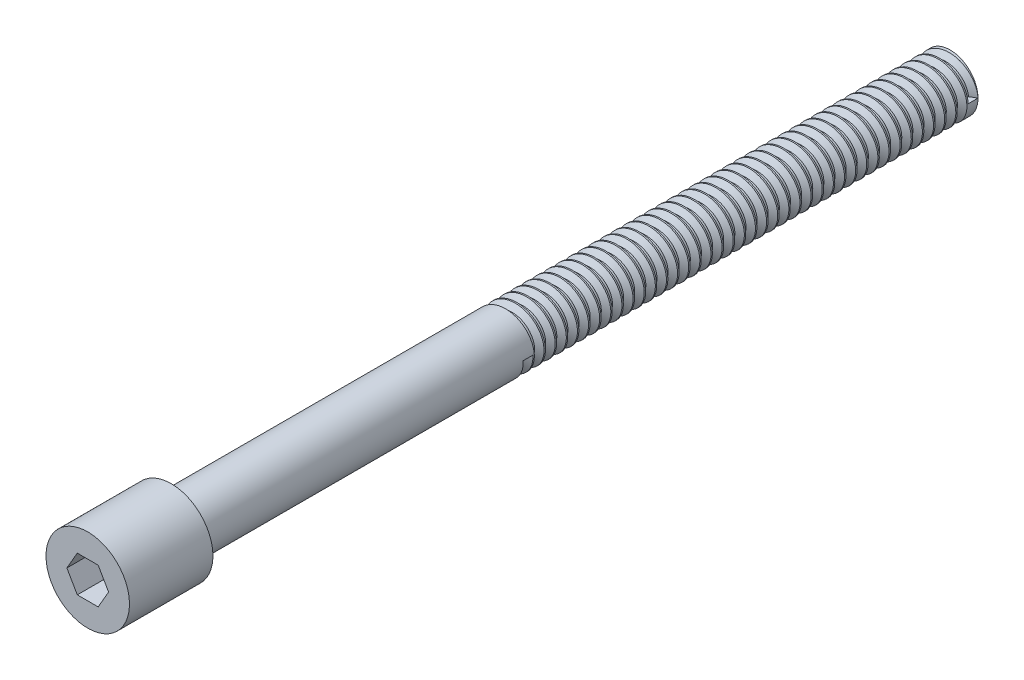
SolidWorks part; units mm, degrees
ref_plane "Front Plane" through (0, 0, 0) normal (0, 0, 1) x (1, 0, 0)
ref_plane "Top Plane" through (0, 0, 0) normal (0, 1, 0) x (1, 0, 0)
ref_plane "Right Plane" through (0, 0, 0) normal (1, 0, 0) x (0, 0, -1)
sketch "Sketch1" plane through (0, 0, 0) normal (0, 0, 1) x (1, 0, 0)
  circle A0 centre (0, 0) radius 3.175
  dimension "D1" = 6.35
extrude "Boss-Extrude1" add sketch "Sketch1" along normal blind 88.9
sketch "Sketch2" plane through (0, 0, 88.9) normal (0, 0, 1) x (1, 0, 0)
  circle A0 centre (0, 0) radius 4.7625
  dimension "D1" = 9.525
extrude "Boss-Extrude2" add sketch "Sketch2" along normal blind 9.525
thread "Thread1" pitch 1.27 method cut profile "Thread Profile1" start angle 0, offset 0, length 50.8, pitch 1.27, diameter 6.35
ref_plane "Plane1" through (3.175, 0, 0) normal (0, -1, 0) x (1, 0, 0)
sketch "Thread Profile1" plane through (3.175, 0, 0) normal (0, -1, 0) x (1, 0, 0)
  line L0 (0, 0) -> (0, 1.27) construction
  line L11 (0, 0) -> (0, 1.1112)
  line L12 (0, 1.1112) -> (-0.6874, 0.7144)
  line L13 (-0.6874, 0.7144) -> (-0.6874, 0.3969)
  line L15 (-0.6874, 0.3969) -> (0, 0)
  line L17 (-0.6874, 0.5556) -> (0, 0.5556) construction
  point P2 (0, 0)
  dimension "Pitch" = 1.27
  dimension "Profile_Angle" = 60
  dimension "Profile_Land" = 0.3175
  dimension "Profile_Height" = 0.6874
sketch "Sketch6" plane through (0, 0, 98.425) normal (0, 0, 1) x (1, 0, 0)
  line L0 (-1.1906, -2.0622) -> (-2.3813, 0)
  line L1 (-2.3813, 0) -> (-1.1906, 2.0622)
  line L2 (-1.1906, 2.0622) -> (1.1906, 2.0622)
  line L3 (1.1906, 2.0622) -> (2.3813, 0)
  line L4 (2.3813, 0) -> (1.1906, -2.0622)
  line L5 (1.1906, -2.0622) -> (-1.1906, -2.0622)
  circle A0 centre (0, 0) radius 2.3813
  dimension "D1" = 4.7625
extrude "Cut-Extrude1" cut sketch "Sketch6" against normal blind 7.9375 contours L5 L4 L3 L2 L1 L0 region at (0, 0, 98.425)
